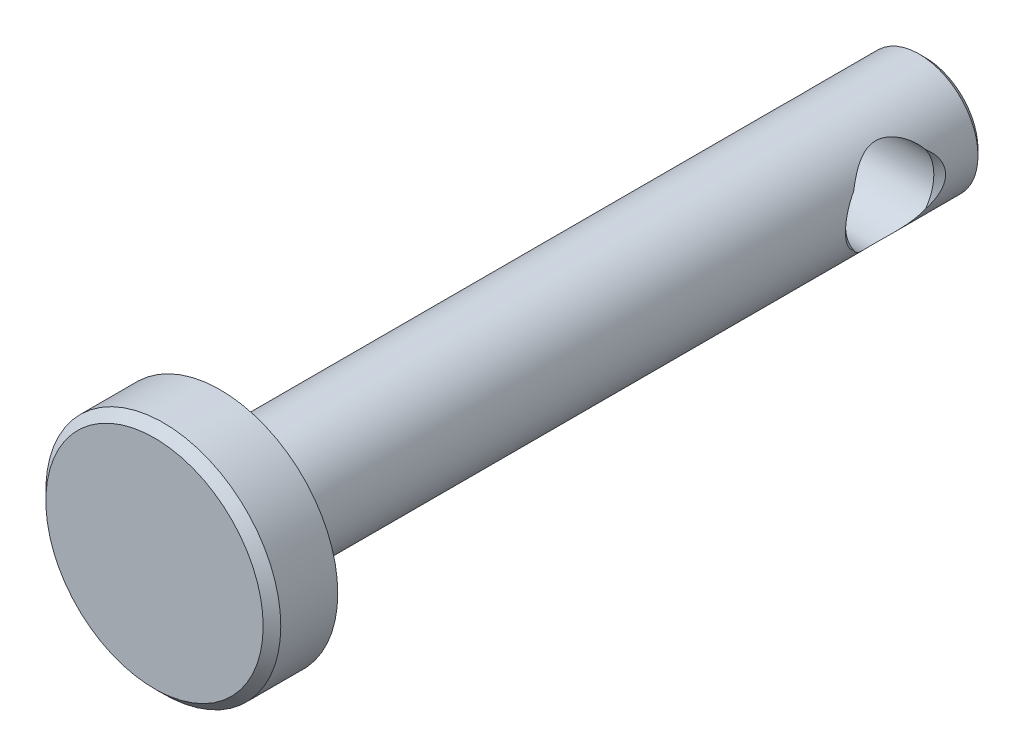
SolidWorks part; units mm, degrees
ref_plane "Front Plane" through (0, 0, 0) normal (0, 0, 1) x (1, 0, 0)
ref_plane "Top Plane" through (0, 0, 0) normal (0, 1, 0) x (1, 0, 0)
ref_plane "Right Plane" through (0, 0, 0) normal (1, 0, 0) x (0, 0, -1)
sketch "Sketch1" plane through (0, 0, 0) normal (1, 0, 0) x (0, 0, -1)
  line L0 (-10.414, 0) -> (10.414, 0) construction
  line L1 (10.414, 1.5875) -> (10.414, -1.5875) construction
  line L2 (-8.636, 3.175) -> (-8.636, -3.175) construction
  line L3 (-10.414, 3.175) -> (-10.414, -3.175) construction
  circle A0 centre (8.0264, 0) radius 1.1938
  point P11 (-8.636, 0)
  dimension "Through Hole Dia." = 2.3876
  dimension "Usable Length" = 15.4686
  dimension "Length" = 19.05
  dimension "Diameter" = 3.175
  dimension "Head Diameter" = 6.35
  dimension "Head Height" = 1.778
sketch "Sketch2" plane through (0, 0, 0) normal (1, 0, 0) x (0, 0, -1)
  line L0 (10.2553, 1.5875) -> (-8.636, 1.5875)
  line L1 (-8.636, 3.175) -> (-8.636, -3.175) construction
  line L2 (-8.636, 1.5875) -> (-8.636, 3.175)
  line L3 (-8.636, 3.175) -> (-10.1759, 3.175)
  line L4 (-10.414, 2.9369) -> (-10.414, 0)
  line L5 (-10.414, 0) -> (10.414, 0)
  line L6 (10.414, 0) -> (10.414, 1.4288)
  line L11 (10.2553, 1.5875) -> (10.414, 1.4288)
  line L12 (-10.1759, 3.175) -> (-10.414, 2.9369)
  dimension "D1" = 45
  dimension "D2" = 0.1588
  dimension "D3" = 0.2381
revolve "Revolve1" add sketch "Sketch2" angle 360 about L5
sketch "Sketch3" plane through (0, 0, 0) normal (1, 0, 0) x (0, 0, -1)
  circle A0 centre (8.0264, 0) radius 1.1938 construction
  circle A1 centre (8.0264, 0) radius 1.1938
  point P3 (9.2202, 0)
  point P4 (6.8326, 0)
extrude "Cut-Extrude1" cut sketch "Sketch3" against normal through all both and the other way through all
fillet "Fillet1" radius 0.1191 1 edges at (1.5875, 0, 8.636)
sketch "Sketch4" plane through (0, 0, 0) normal (0, 1, 0) x (1, 0, 0)
  line L0 (0, 8.0264) -> (-3.0819, 8.0264) construction
  line L1 (-1.5875, 9.3789) -> (-1.27, 9.0615)
  line L2 (-1.5875, 10.2553) -> (-1.5875, 9.2202) construction
  line L3 (-1.27, 9.0615) -> (-1.5875, 9.0615)
  line L4 (-1.5875, 9.0615) -> (-1.5875, 9.3789)
  line L5 (0, 9.2202) -> (-1.5875, 9.2202) construction
  line L6 (0, 8.0264) -> (0, 9.2202) construction
  line L7 (0, 6.8326) -> (0, 9.2202) construction
  line L8 (1.5875, 9.0614) -> (1.5875, 9.3789)
  line L9 (1.27, 9.0615) -> (1.5875, 9.0614)
  line L10 (1.5875, 9.3789) -> (1.27, 9.0615)
  dimension "D1" = 45
  dimension "D2" = 0.3175
revolve "Cut-Revolve1" cut sketch "Sketch4" angle 360 about L0
ref_axis "Center Axis 1" through (-1.4287, 0, -8.0264) along (1, 0, 0)
ref_plane "Contact Plane 1" through (0, 0, 8.636) normal (0, 0, -1) x (-1, 0, 0)
equation "\"D2@Sketch2\"=\"Diameter@Sketch1\"*.05"
equation "\"D3@Sketch2\"=\"Head Diameter@Sketch1\"*.0375"
equation "\"D1@Fillet1\"=\"Diameter@Sketch1\"*.0375"
equation "\"D2@Sketch4\"=\"Diameter@Sketch1\"*.1"
